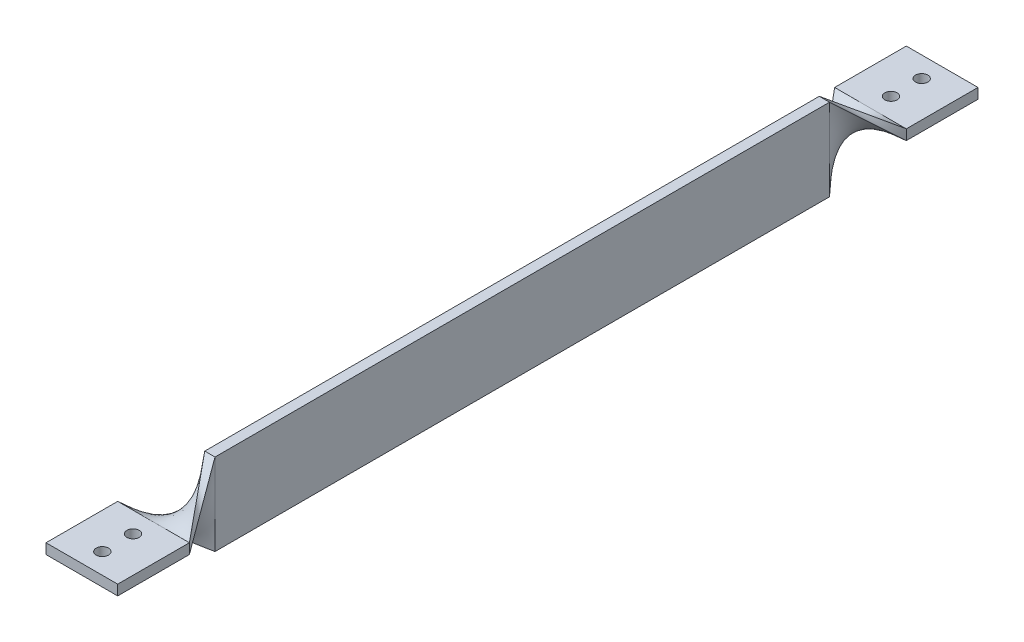
SolidWorks part; units mm, degrees
ref_plane "Płaszczyzna przednia" through (0, 0, 0) normal (0, 0, 1) x (1, 0, 0)
ref_plane "Płaszczyzna górna" through (0, 0, 0) normal (0, 1, 0) x (1, 0, 0)
ref_plane "Płaszczyzna prawa" through (0, 0, 0) normal (1, 0, 0) x (0, 0, -1)
sketch "Szkic1" plane through (0, 0, 0) normal (0, 0, 1) x (1, 0, 0)
  line L1 (0, 0) -> (35, 0)
  line L2 (0, 0) -> (0, 5)
  line L3 (0, 5) -> (35, 5)
  line L4 (35, 0) -> (35, 5)
  dimension "D1" = 35
  dimension "D2" = 5
extrude "Dodanie-wyciągnięcie1" add sketch "Szkic1" along normal mid plane 35
ref_plane "Płaszczyzna1" through (0, 0, 42.5) normal (0, 0, 1) x (1, 0, 0)
sketch "Szkic2" plane through (0, 0, 42.5) normal (0, 0, 1) x (1, 0, 0)
  line L0 (0, 5) -> (0, 0) construction
  line L1 (17.5, 22.5) -> (22.5, 22.5)
  line L2 (17.5, 22.5) -> (17.5, -17.5)
  line L3 (17.5, -17.5) -> (22.5, -17.5)
  line L4 (22.5, 22.5) -> (22.5, -17.5)
  line L5 (0, 0) -> (35, 0) construction
  dimension "D1" = 5
  dimension "D2" = 40
  dimension "D3" = 17.5
  dimension "D4" = 17.5
extrude "Dodanie-wyciągnięcie2" add sketch "Szkic2" along normal blind 300 separate body
loft "Wyciągnięcie po profilach3" add section face at (17.5, 2.5, 17.5) section face at (20, 2.5, 42.5) connector at (35, 0, 17.5) connector at (22.5, 22.5, 42.5)
ref_plane "Płaszczyzna2" through (0, 0, 367.5) normal (0, 0, 1) x (1, 0, 0)
sketch "Szkic5" plane through (0, 0, 367.5) normal (0, 0, 1) x (1, 0, 0)
  line L1 (0, 5) -> (35, 5)
  line L2 (0, 5) -> (0, 0)
  line L3 (0, 0) -> (35, 0)
  line L4 (35, 5) -> (35, 0)
extrude "Dodanie-wyciągnięcie3" add sketch "Szkic5" along normal blind 35 separate body
loft "Wyciągnięcie po profilach5" add section face at (17.5, 2.5, 367.5) section face at (20, 2.5, 342.5) connector at (35, 0, 367.5) connector at (22.5, 22.5, 342.5)
sketch "Szkic7" plane through (0, 5, 0) normal (0, 1, 0) x (1, 0, 0)
  line L0 (35, -402.5) -> (35, -367.5) construction
  line L1 (-55, -367.5) -> (55, -367.5) construction
  circle A0 centre (17.5, -377.5) radius 3
  circle A1 centre (17.5, -392.5) radius 3
  dimension "D1" = 6
  dimension "D2" = 17.5
  dimension "D5" = 17.5
  dimension "D6" = 6
  dimension "D3" = 10
  dimension "D4" = 15
sketch "Szkic8" plane through (0, 5, 0) normal (0, 1, 0) x (1, 0, 0)
  line L0 (35, -17.5) -> (0, -17.5) construction
  line L1 (35, -17.5) -> (35, 17.5) construction
  line L2 (0, -17.5) -> (0, 17.5) construction
  circle A0 centre (17.5, -7.5) radius 3
  circle A2 centre (17.5, 7.5) radius 3
  dimension "D1" = 6
  dimension "D2" = 10
  dimension "D3" = 17.5
  dimension "D4" = 6
  dimension "D5" = 15
  dimension "D6" = 17.5
sketch "Szkic12" plane through (0, 5, 0) normal (0, 1, 0) x (1, 0, 0)
extrude "Wytnij-wyciągnięcie3" cut sketch "Szkic7" against normal blind 20 contours A1 | A0
extrude "Wytnij-wyciągnięcie4" cut sketch "Szkic8" against normal blind 20 contours A2 | A0
